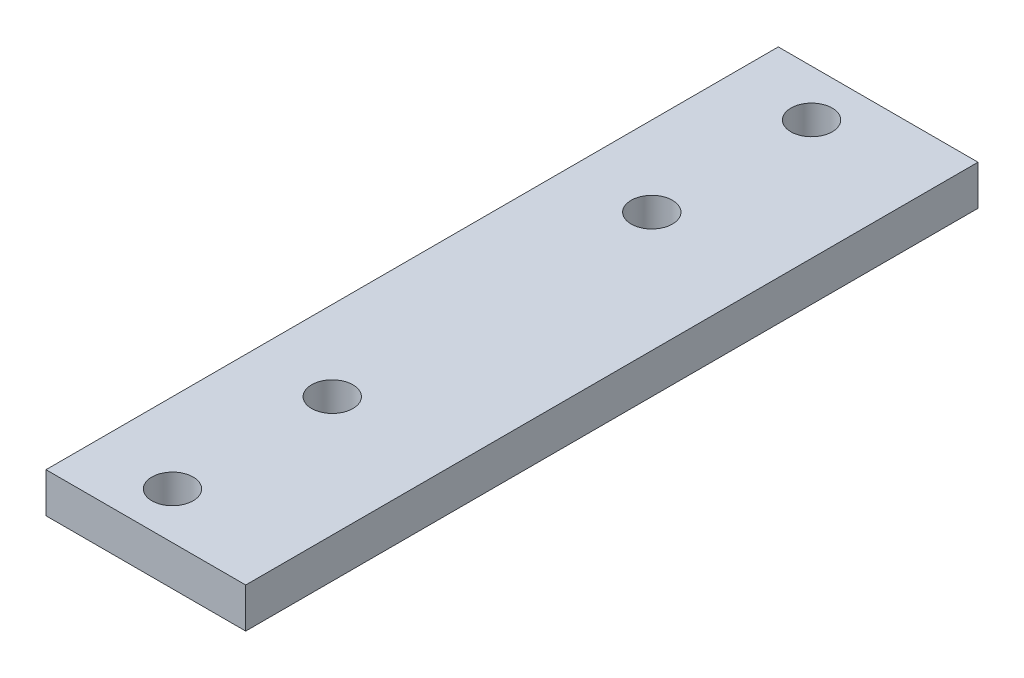
SolidWorks part; units mm, degrees
ref_plane "Front Plane" through (0, 0, 0) normal (0, 0, 1) x (1, 0, 0)
ref_plane "Top Plane" through (0, 0, 0) normal (0, 1, 0) x (1, 0, 0)
ref_plane "Right Plane" through (0, 0, 0) normal (1, 0, 0) x (0, 0, -1)
sketch "Sketch1" plane through (0, 0, 0) normal (0, 0, 1) x (1, 0, 0)
  line L0 (-35, 0) -> (35, 0)
  circle A0 centre (0, 0) radius 35
  dimension "D1" = 70
extrude "Boss-Extrude1" add sketch "Sketch1" along normal blind 45 contours L0 A0 region at (0, -14.8545, 0)
sketch "Sketch2" plane through (0, 0, 0) normal (0, 1, 0) x (1, 0, 0)
  line L0 (-35, 0) -> (35, 0) construction
  line L1 (-31, -4) -> (0.5147, -4)
  line L2 (-31, -4) -> (-31, -41)
  line L3 (-31, -41) -> (0, -41)
  line L5 (-35, -45) -> (35, -45) construction
  line L6 (-35, -45) -> (-35, 0) construction
  line L7 (0, 0) -> (0, -45) construction
  line L8 (-31, -4) -> (0.5147, -4)
  line L9 (-31, -4) -> (-31, -41)
  line L10 (-31, -41) -> (0, -41)
  line L13 (-31, -4) -> (0, -4)
  line L14 (-31, -4) -> (-31, -41)
  line L15 (-31, -41) -> (0, -41)
  line L16 (0, -4) -> (0, -41)
  dimension "D1" = 4
  dimension "D2" = 4
  dimension "D3" = 4
ref_axis "Axis1" through (0, 0, 45) along (0, 0, -1)
revolve "Cut-Revolve1" cut sketch "Sketch2" angle 360 about L7 region at (-15.5, 0, 22.5)
sketch "Sketch3" plane through (0, 0, 45) normal (0, 0, 1) x (1, 0, 0)
  line L0 (-17.5, 0) -> (-17.5, -35)
  line L1 (0, 0) -> (-35, 0)
  line L4 (0, 0) -> (0, -35)
  line L9 (-35, -35) -> (-17.5, -35)
  line L10 (-35, 0) -> (-35, -35)
  line L11 (-35, 0) -> (-17.5, 0)
  line L12 (-35, -35) -> (0, -35)
  line L13 (-35, 0) -> (-35, -35)
  arc A0 (-35, 0) -> (35, 0) centre (0, 0) ccw construction
  line M1 (35, 0) -> (-35, 0)
  arc M2 (-35, 0) -> (35, 0) centre (0, 0) ccw
extrude "Boss-Extrude3" add sketch "Sketch3" against normal blind 45 contours L10 L9 L0 M2 | L0 L12 M2 | L0 M1 M2 region at (-24.6757, -11.8721, 45) region at (-13.1858, -33.611, 45) region at (-28.7561, -26.4591, 45)
sketch "Sketch4" plane through (-35, 0, 0) normal (-1, 0, 0) x (0, 0, 1)
  line L0 (0, -35) -> (45, -35) construction
  line L2 (0, 0) -> (0, -35) construction
  line L3 (0, 0) -> (45, 0) construction
  line L4 (45, 0) -> (22.5, 0) construction
  line L5 (22.5, 0) -> (22.5, -35) construction
  circle A0 centre (10, -17.5) radius 5.05
  circle A1 centre (35, -17.5) radius 5.05
  dimension "D1" = 10.1
  dimension "D2" = 17.5
  dimension "D3" = 10
extrude "Cut-Extrude1" cut sketch "Sketch4" against normal blind 12
sketch "Sketch5" plane through (0, 0, 0) normal (0, 0, -1) x (-1, 0, 0)
  line L0 (35, -35) -> (0, -35) construction
  line L1 (35, 0) -> (30, 0)
  line L2 (35, 0) -> (35, -35)
  line L3 (35, -35) -> (30, -35)
  line L4 (30, 0) -> (30, -35)
  dimension "D1" = 5
extrude "Cut-Extrude2" cut sketch "Sketch5" against normal through all
sketch "Sketch6" plane through (0, 0, 41) normal (0, 0, -1) x (-1, 0, 0)
  line L0 (0, -31) -> (0, 0)
  line L1 (0, 0) -> (-31, 0)
  line L2 (0, 0) -> (-12.5, 0)
  line L3 (-12.5, 0) -> (-12.5, -28.3681)
  line L5 (17.5, 0) -> (12.5, 0)
  line L6 (17.5, 0) -> (17.5, -28.3681)
  line L7 (17.5, -28.3681) -> (12.5, -28.3681)
  line L8 (12.5, 0) -> (12.5, -28.3681)
  circle A0 centre (0, 0) radius 31
  line M1 (17.5, -25.5881) -> (17.5, 0)
  line M2 (17.5, 0) -> (-31, 0)
  arc M3 (-31, 0) -> (17.5, -25.5881) centre (0, 0) ccw
  dimension "D1" = 12.5
  dimension "D2" = 5
extrude "Boss-Extrude5" add sketch "Sketch6" along normal blind 37 contours L3 L1 M3 | L8 M2 M3 M1 region at (20.1294, -11.2411, 41) region at (-14.9573, -13.5514, 41)
sketch "Sketch7" plane through (0, 0, 0) normal (0, 0, -1) x (-1, 0, 0)
  line L5 (-35, 0) -> (-12.5, 0)
  line L6 (-35, 0) -> (-35, -7.441)
  line L7 (-35, -7.441) -> (-12.5, -7.441)
  line L8 (-12.5, 0) -> (-12.5, -7.441)
  line L9 (0, 0) -> (0, 11.2128) construction
  line L10 (35, 0) -> (35, -7.441)
  line L11 (35, 0) -> (12.5, 0)
  line L12 (35, -7.441) -> (12.5, -7.441)
  line L13 (12.5, 0) -> (12.5, -7.441)
  circle A0 centre (0, 0) radius 35
  line M6 (30, -35) -> (30, 0)
  line M7 (30, 0) -> (-35, 0)
  arc M8 (-35, 0) -> (0, -35) centre (0, 0) ccw
  dimension "D1" = 22.5
extrude "Boss-Extrude6" add sketch "Sketch7" along normal blind 5 contours L8 L7 M7 M8 | L13 L12 M7 M6 region at (23.6185, -3.6982, 0) region at (-21.25, -3.7205, 0)
ref_plane "Plane1" through (0, 0, 22.5) normal (0, 0, -1) x (-1, 0, 0)
mirror "Mirror1" about plane through (0, 0, 22.5) normal (0, 0, -1) of "Boss-Extrude6"
sketch "Sketch9" plane through (0, 0, 0) normal (0, 1, 0) x (1, 0, 0)
  line L0 (12.5, -50) -> (35, -50) construction
  line L5 (35, 5) -> (20, 5)
  line L6 (35, 5) -> (35, -50)
  line L7 (35, -50) -> (20, -50)
  line L8 (20, 5) -> (20, -50)
  line L9 (-30, -50) -> (-12.5, -50) construction
  line L10 (-30, 5) -> (-20, 5)
  line L11 (-30, 5) -> (-30, -50)
  line L12 (-30, -50) -> (-20, -50)
  line L13 (-20, 5) -> (-20, -50)
  dimension "D1" = 10
  dimension "D2" = 15
extrude "Boss-Extrude7" add sketch "Sketch9" along normal blind 3
sketch "Sketch12" plane through (0, 3, 0) normal (0, 1, 0) x (1, 0, 0)
  line L0 (35, -50) -> (35, 5) construction
  line L1 (35, 5) -> (20, 5) construction
  line L3 (19.25, -22.5) -> (-19.25, -22.5) construction
  line L4 (35, -22.5) -> (0, -22.5) construction
  line L6 (-30, 5) -> (-30, -50) construction
  line L7 (0, -22.5) -> (0, -55.2431) construction
  circle A0 centre (26, 1.5) radius 1.55
  circle A1 centre (26, -10.5) radius 1.55
  circle A2 centre (26, -34.5) radius 1.55
  circle A3 centre (26, -46.5) radius 1.55
  circle A7 centre (-26, 1.5) radius 1.55
  circle A8 centre (-26, -10.5) radius 1.55
  circle A9 centre (-26, -34.5) radius 1.55
  circle A10 centre (-26, -46.5) radius 1.55
  dimension "D1" = 3.1
  dimension "D2" = 9
  dimension "D3" = 3.5
  dimension "D4" = 12
  dimension "D5" = 9
  dimension "D6" = 3.1
  dimension "D7" = 4
  dimension "D8" = 2
extrude "Cut-Extrude5" cut sketch "Sketch12" against normal blind 5
sketch "Sketch13" plane through (35, 0, 0) normal (1, 0, 0) x (0, 0, -1)
  line L1 (-50, 3) -> (-43, 3)
  line L2 (-50, 3) -> (-50, -4)
  line L3 (-50, -4) -> (-43, -4)
  line L4 (-43, 3) -> (-43, -4)
  line L6 (-44.95, -2) -> (-44.95, 3) construction
  line L7 (-44.95, -2) -> (-48.05, -2) construction
  line L8 (-50, 3) -> (5, 3) construction
  line L9 (-38, 3) -> (-31, 3)
  line L10 (-38, 3) -> (-38, -4)
  line L11 (-38, -4) -> (-31, -4)
  line L12 (-31, 3) -> (-31, -4)
  line L13 (-36.05, 3) -> (-36.05, -2) construction
  line L14 (-32.95, -2) -> (-32.95, 3) construction
  line L15 (-32.95, -2) -> (-36.05, -2) construction
  line L16 (-22.5, 3) -> (-22.5, 8.3556) construction
  line L17 (-22.5, -19.25) -> (-22.5, 19.25) construction
  line L18 (-14, 3) -> (-14, -4)
  line L19 (-7, -4) -> (-14, -4)
  line L20 (-7, 3) -> (-7, -4)
  line L21 (-7, 3) -> (-14, 3)
  line L22 (-2, 3) -> (-2, -4)
  line L23 (5, -4) -> (-2, -4)
  line L24 (5, 3) -> (5, -4)
  line L25 (5, 3) -> (-2, 3)
  line L27 (-50, 3) -> (5, 3)
  line L28 (-50, 3) -> (-50, 0)
  line L29 (-50, 0) -> (5, 0)
  line L30 (5, 3) -> (5, 0)
  line M9 (-50, 0) -> (5, 0)
  dimension "D1" = 1.95
  dimension "D2" = 2
  dimension "D3" = 1.95
  dimension "D4" = 1.95
  dimension "D5" = 2
extrude "Cut-Extrude6" cut sketch "Sketch13" against normal through all contours L4 L2 L3 M9 | L12 L10 L11 M9 | L20 L18 L19 M9 | L24 L22 L23 M9 region at (35, -2, 46.5) region at (35, -2, 34.5) region at (35, -2, 10.5) region at (35, -2, -1.5)
sketch "Sketch14" plane through (0, 0, 50) normal (0, 0, 1) x (1, 0, 0)
  line L1 (-17.0942, 0) -> (35.3006, 0)
  line L2 (-30, 0) -> (-30, -35.4874)
  line L3 (-30, -35.4874) -> (35.3006, -35.4874)
  line L4 (35.3006, 0) -> (35.3006, -35.4874)
  line L6 (-30, 0) -> (-30, 9.0518)
  line L7 (-30, 9.0518) -> (-17.0942, 9.0518)
  line L8 (-17.0942, 0) -> (-17.0942, 9.0518)
extrude "Cut-Extrude7" cut sketch "Sketch14" against normal through all
